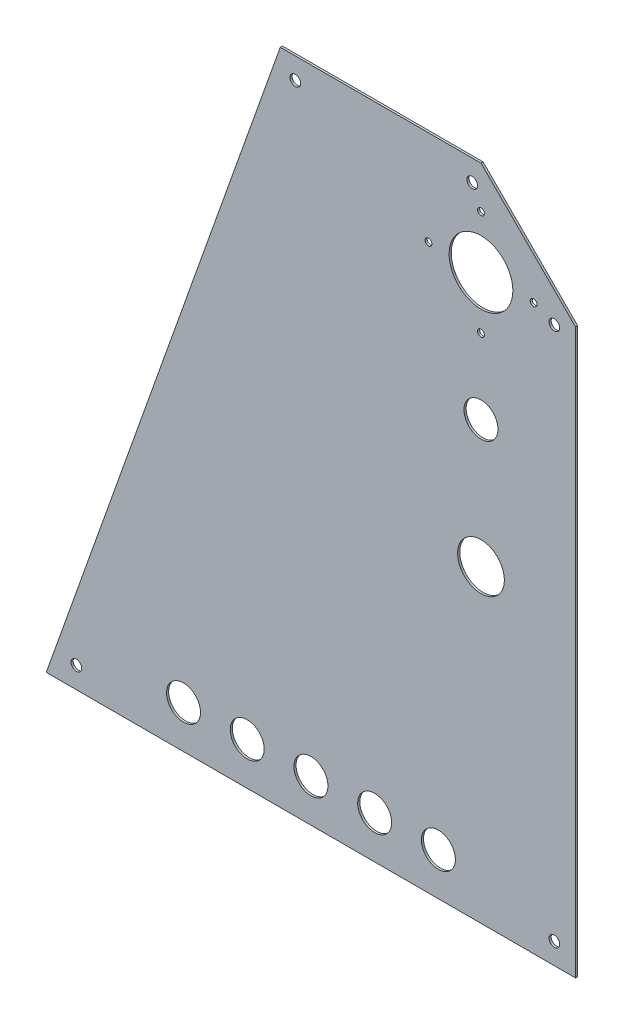
SolidWorks part; units mm, degrees
ref_plane "Front Plane" through (0, 0, 0) normal (1, 0, 0) x (0, 1, 0)
ref_plane "Top Plane" through (0, 0, 0) normal (0, 0, 1) x (0, 1, 0)
ref_plane "Right Plane" through (0, 0, 0) normal (0, 1, 0) x (-1, 0, 0)
sketch "Sketch1" plane through (0, 0, 0) normal (0, 0, 1) x (0, 1, 0)
  line L1 (-155, -125) -> (155, -125)
  line L2 (-155, -125) -> (-155, 125)
  line L3 (-155, 125) -> (155, 125)
  line L4 (155, -125) -> (155, 125)
  line L5 (-155, -125) -> (155, 125) construction
  line L6 (-155, 125) -> (155, -125) construction
  point P0 (0, 0)
  dimension "D1" = 310
  dimension "D2" = 250
extrude "Boss-Extrude1" add sketch "Sketch1" along normal blind 1
sketch "Sketch2" plane through (0, 0, 1) normal (0, 0, 1) x (0, -1, 0)
  line L0 (-155, -14.0477) -> (155, -124.2339)
  line L1 (-155, 125) -> (-155, -125) construction
  line L4 (155, -124.2339) -> (155, 125)
  line L5 (155, 125) -> (-110.4523, 125)
  line L6 (155, 125) -> (-155, 125) construction
  line L7 (-110.4523, 125) -> (-155, 80.4523)
  line L8 (-155, 80.4523) -> (-155, -14.0477)
  line L9 (-155, 80.4523) -> (-155, 125) construction
  line L10 (-155, 125) -> (-110.4523, 125) construction
  dimension "D1" = 63
  dimension "D2" = 329
  dimension "D3" = 94.5
extrude "Cut-Extrude1" cut sketch "Sketch2" against normal through all flip side to cut
sketch "Sketch3" plane through (0, 0, 1) normal (0, 0, 1) x (0, -1, 0)
  line L0 (-155, 80.4523) -> (155, 80.4523) construction
  line L2 (155, -124.2339) -> (155, 125) construction
  line L4 (-110.4523, 125) -> (-155, 80.4523) construction
  line L5 (-155, 80.4523) -> (-110.4523, 80.4523) construction
  line L6 (-110.4523, 80.4523) -> (-110.4523, 125) construction
  line L7 (-110.4523, 55.7035) -> (-85.7035, 80.4523) construction
  line L8 (-85.7035, 80.4523) -> (-110.4523, 105.201) construction
  line L9 (-110.4523, 105.201) -> (-135.201, 80.4523) construction
  line L10 (-135.201, 80.4523) -> (-110.4523, 55.7035) construction
  circle A0 centre (-110.4523, 80.4523) radius 15
  circle A1 centre (-50.4523, 80.4523) radius 8
  circle A2 centre (9.5477, 80.4523) radius 11
  circle A3 centre (-110.4523, 55.7035) radius 1.6
  circle A4 centre (-135.201, 80.4523) radius 1.6
  circle A5 centre (-110.4523, 105.201) radius 1.6
  circle A6 centre (-85.7035, 80.4523) radius 1.6
  dimension "D2" = 30
  dimension "D1" = 16
  dimension "D3" = 22
  dimension "D8" = 3.2
  dimension "D4" = 60
  dimension "D5" = 60
  dimension "D6" = 90
  dimension "D7" = 35
extrude "Cut-Extrude2" cut sketch "Sketch3" against normal through all
sketch "Sketch4" plane through (0, 0, 1) normal (0, 0, 1) x (0, -1, 0)
  line L0 (135, -117.1251) -> (135, 125) construction
  line L1 (-155, -14.0477) -> (155, -124.2339) construction
  line L2 (155, 125) -> (-110.4523, 125) construction
  line L3 (155, -124.2339) -> (155, 125) construction
  circle A0 centre (135, -59.617) radius 8
  circle A1 centre (135, -29.617) radius 8
  circle A2 centre (135, 0.383) radius 8
  circle A3 centre (135, 30.383) radius 8
  circle A4 centre (135, 60.383) radius 8
  point P22 (155, 0.383)
  dimension "D2" = 16
  dimension "D3" = 30
  dimension "D4" = 30
  dimension "D5" = 30
  dimension "D6" = 30
  dimension "D1" = 20
extrude "Cut-Extrude3" cut sketch "Sketch4" against normal through all
sketch "Sketch5" plane through (0, 0, 1) normal (0, 0, 1) x (0, -1, 0)
  line L0 (155, -124.2339) -> (155, 125) construction
  line L3 (155, 125) -> (-110.4523, 125) construction
  line L4 (-155, 80.4523) -> (-155, -14.0477) construction
  line L5 (-155, -14.0477) -> (155, -124.2339) construction
  line L6 (-110.4523, 125) -> (-155, 80.4523) construction
  circle A0 centre (145, -110.0666) radius 2.5
  circle A1 centre (-145, -6.9892) radius 2.5
  circle A2 centre (-145, 76.3101) radius 2.5
  circle A3 centre (145, 115) radius 2.5
  circle A4 centre (-106.3101, 115) radius 2.5
  point P18 (-110.8086, 110.5015)
  point P19 (-113.5898, 107.7204)
  point P25 (-100.4523, 113.9498)
  point P26 (-100.4523, 112.8262)
  dimension "D1" = 5
  dimension "D2" = 10
  dimension "D3" = 10
  dimension "D4" = 10
  dimension "D5" = 10
  dimension "D6" = 10
  dimension "D7" = 10
  dimension "D8" = 10
  dimension "D9" = 10
  dimension "D10" = 10
  dimension "D11" = 10
extrude "Cut-Extrude4" cut sketch "Sketch5" against normal through all
